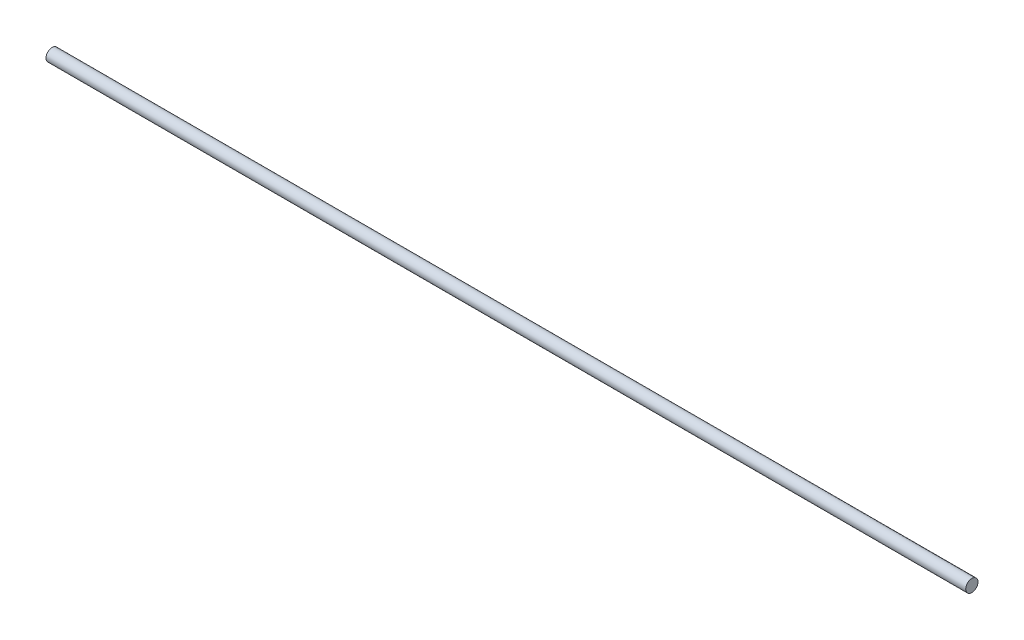
SolidWorks part; units mm, degrees
ref_plane "Front Plane" through (0, 0, 0) normal (0, 0, 1) x (1, 0, 0)
ref_plane "Top Plane" through (0, 0, 0) normal (0, 1, 0) x (1, 0, 0)
ref_plane "Right Plane" through (0, 0, 0) normal (1, 0, 0) x (0, 0, -1)
sketch "Sketch1" plane through (0, 0, 0) normal (1, 0, 0) x (0, 0, -1)
  circle A0 centre (0, 0) radius 4
  dimension "D1" = 8
extrude "Boss-Extrude1" add sketch "Sketch1" along normal blind 300 and the other way blind 300
ref_axis "Axis1" through (300, 0, 0) along (-1, 0, 0)
